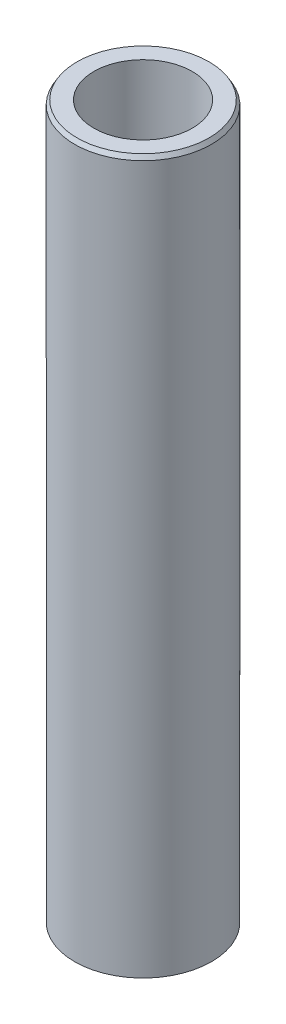
SolidWorks part; units mm, degrees
ref_plane "Front Plane" through (0, 0, 0) normal (0, 0, 1) x (1, 0, 0)
ref_plane "Top Plane" through (0, 0, 0) normal (0, 1, 0) x (1, 0, 0)
ref_plane "Right Plane" through (0, 0, 0) normal (1, 0, 0) x (0, 0, -1)
sketch "Sketch1" plane through (0, 0, 0) normal (0, 1, 0) x (1, 0, 0)
  circle A0 centre (0, 0) radius 57.5
  dimension "SHAFT_OD" = 115
extrude "Boss-Extrude1" add sketch "Sketch1" along normal blind 600
sketch "Sketch2" plane through (0, 0, 0) normal (0, 1, 0) x (1, 0, 0)
  circle A0 centre (0, 0) radius 41.3142
  dimension "BORE_D" = 82.6285
extrude "Cut-Extrude1" cut sketch "Sketch2" along normal through all
chamfer "Chamfer1" distance 3.6249 angle 30 2 edges at (0, 600, 57.5) (0, 0, 57.5) first distance on face at (0, 600, 57.5) first distance on face at (0, 0, 41.3142)
